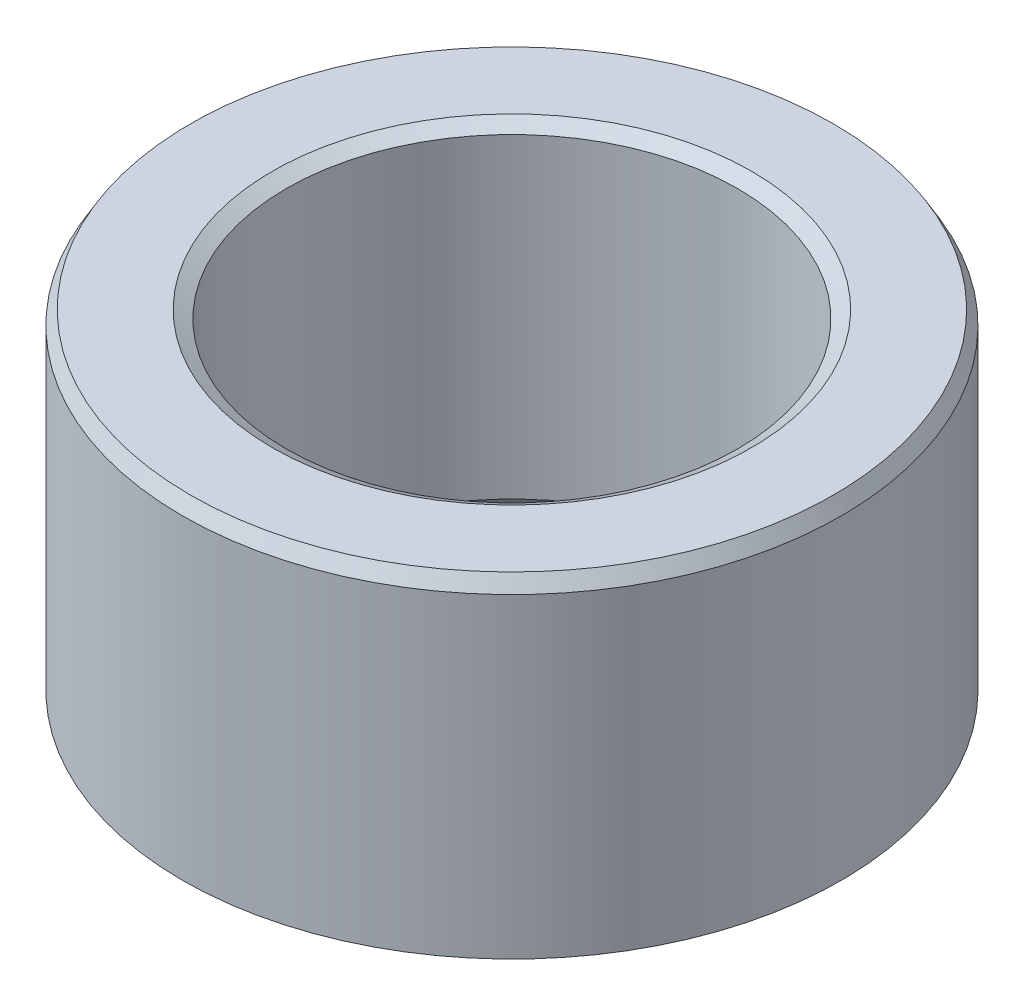
SolidWorks part; units mm, degrees
ref_plane "Front Plane" through (0, 0, 0) normal (0, 0, 1) x (1, 0, 0)
ref_plane "Top Plane" through (0, 0, 0) normal (0, 1, 0) x (1, 0, 0)
ref_plane "Right Plane" through (0, 0, 0) normal (1, 0, 0) x (0, 0, -1)
sketch "Sketch1" plane through (0, 0, 0) normal (0, 1, 0) x (1, 0, 0)
  circle A0 centre (0, 0) radius 17.5
  dimension "SLEEVE_OD" = 35
extrude "Boss-Extrude1" add sketch "Sketch1" along normal blind 17.9272
sketch "Sketch2" plane through (0, 0, 0) normal (0, 1, 0) x (1, 0, 0)
  circle A0 centre (0, 0) radius 11.9802
  dimension "BORE_D" = 23.9605
extrude "Cut-Extrude1" cut sketch "Sketch2" along normal through all
chamfer "Chamfer1" distance 0.7392 angle 30 4 edges at (0, 17.9272, 11.9802) (0, 0, 11.9802) (0, 0, 17.5) (0, 17.9272, 17.5) first distance on face at (0, 17.9272, 11.9802) first distance on face at (0, 0, 11.9802) first distance on face at (0, 17.9272, 17.5)
